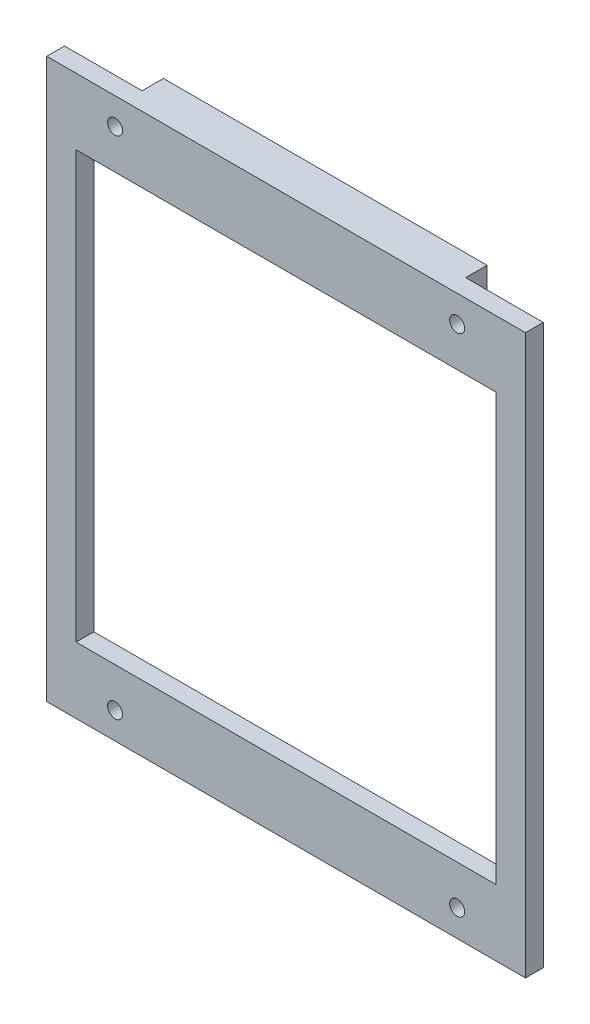
SolidWorks part; units mm, degrees
ref_plane "Front Plane" through (0, 0, 0) normal (0, 0, 1) x (1, 0, 0)
ref_plane "Top Plane" through (0, 0, 0) normal (0, 1, 0) x (1, 0, 0)
ref_plane "Right Plane" through (0, 0, 0) normal (1, 0, 0) x (0, 0, -1)
sketch "Sketch1" plane through (0, 0, 6.1) normal (0, 0, 1) x (1, 0, 0)
  line L0 (-67.25, 78.5) -> (67.25, 78.5)
  line L1 (67.25, 78.5) -> (67.25, -78.5)
  line L2 (-67.25, -78.5) -> (-67.25, 78.5)
  line L3 (-67.1, 0) -> (-59.525, 0) construction
  line L4 (67.25, 5) -> (67.25, 83.5) construction
  line L5 (74.675, 0) -> (82.25, 0) construction
  line L6 (-74.675, 0) -> (-82.25, 0) construction
  line L7 (-59, -59.9) -> (59, -59.9)
  line L8 (-67.25, -78.5) -> (67.25, -78.5)
  line L21 (59, 59.9) -> (59, 0)
  line L22 (-59, 59.9) -> (59, 59.9)
  line L23 (-59, 0) -> (-59, 59.9)
  line L24 (59, 59.9) -> (59, -59.9)
  line L25 (-59, 59.9) -> (59, 59.9)
  line L26 (-59, -59.9) -> (-59, 59.9)
  circle A0 centre (-48.05, 70.9904) radius 2.1
  circle A1 centre (48.05, 70.9904) radius 2.1
  circle A2 centre (48.05, 70.9904) radius 2.1 construction
  circle A3 centre (-48.05, 70.9904) radius 2.1 construction
  circle A4 centre (48.05, -70.9904) radius 2.1
  circle A5 centre (-48.05, -70.9904) radius 2.1
  point P28 (-67.25, 0)
  point P29 (67.25, 0)
  dimension "D1" = 1
extrude "Boss-Extrude1" add sketch "Sketch1" along normal blind 5
sketch "Sketch2" plane through (0, 0, 6.1) normal (0, 0, -1) x (-1, 0, 0)
  line L9 (-45.4729, 60.9) -> (-45.4729, 66.95)
  line L10 (-45.4729, 66.95) -> (45.475, 66.95)
  line L11 (45.475, 66.95) -> (45.475, 60.9)
  line L12 (45.475, 60.9) -> (-45.4729, 60.9)
  line L14 (-45.45, 66.925) -> (-45.425, 31.4857) construction
  line L16 (45.45, 66.925) -> (-45.45, 66.925) construction
  line L17 (-10.2, 60.925) -> (-45.4458, 60.925) construction
  line L18 (-74.675, 0) -> (-82.25, 0) construction
  line L19 (45.475, -60.9) -> (-45.4729, -60.9)
  line L20 (45.475, -66.95) -> (45.475, -60.9)
  line L21 (-45.4729, -66.95) -> (45.475, -66.95)
  line L22 (-45.4729, -60.9) -> (-45.4729, -66.95)
  point P4 (-45.4729, 63.925)
  dimension "D1" = 0.025
  dimension "D2" = 0.025
  dimension "D3" = 0.025
  dimension "D4" = 0.025
extrude "Cut-Extrude1" cut sketch "Sketch2" against normal up to surface (1.57 mm away)
sketch "Sketch3" plane through (0, 0, 0.1) normal (0, 0, 1) x (1, 0, 0)
  line L0 (-45.45, -78.5) -> (45.45, -78.5)
  line L1 (-67.25, -78.5) -> (67.25, -78.5) construction
  line L2 (-45.45, -150) -> (-45.45, -31.4857) construction
  line L3 (45.45, -31.4857) -> (45.45, -150) construction
  line L4 (45.45, -78.5) -> (45.45, -66.95)
  line L5 (45.45, -66.95) -> (-45.45, -66.95)
  line L6 (-45.45, -66.95) -> (-45.45, -78.5)
  line L7 (-45.45, -66.925) -> (45.45, -66.925) construction
  line L8 (-74.675, 0) -> (-82.25, 0) construction
  line L9 (-45.45, 66.95) -> (-45.45, 78.5)
  line L10 (45.45, 66.95) -> (-45.45, 66.95)
  line L11 (45.45, 78.5) -> (45.45, 66.95)
  line L12 (-45.45, 78.5) -> (45.45, 78.5)
  dimension "D1" = 0.025
extrude "Boss-Extrude2" add sketch "Sketch3" along normal up to surface (6 mm away) up to face at (-0.0011, 63.925, 6.1)
